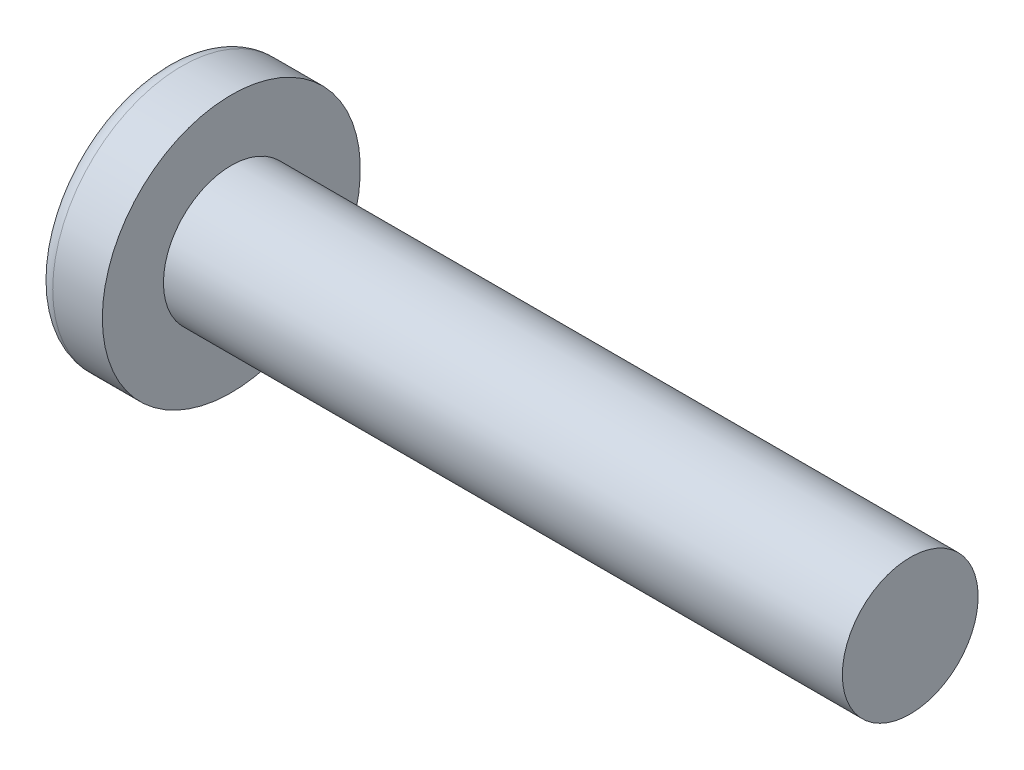
SolidWorks part; units mm, degrees
ref_plane "Plane1" through (0, 0, 0) normal (0, 0, 1) x (1, 0, 0)
ref_plane "Plane2" through (0, 0, 0) normal (0, 1, 0) x (1, 0, 0)
ref_plane "Plane3" through (0, 0, 0) normal (1, 0, 0) x (0, 0, -1)
other "Configuration Table"
sketch "BodySke" plane through (0, 0, 0) normal (0, 0, 1) x (1, 0, 0)
  line L0 (3.7, 2.5) -> (3.7, 4.75)
  line L1 (4.5, 6.35) -> (4.5, -3.175) construction
  line L2 (-25.4, 0) -> (127, 0) construction
  line L3 (28.7, 0) -> (0, 0)
  line L4 (3.7, 2.5) -> (28.7, 2.5)
  line L5 (28.7, 2.5) -> (28.7, 0)
  line L6 (1.8732, 4.75) -> (3.7, 4.75)
  line L7 (3.7, -2.5) -> (28.7, -2.5) construction
  line L8 (3.7, 6.35) -> (3.7, -3.175) construction
  arc A0 (1.3764, 4.4865) -> (0, 0) centre (8, 0) ccw
  arc A2 (1.3764, 4.4865) -> (1.8732, 4.75) centre (1.8732, 4.15) cw
  dimension "Head_fillet_rad" = 0.6
  dimension "Length" = 25
  dimension "Head_ht" = 3.7
  dimension "Head_dia" = 9.5
  dimension "Diameter" = 5
  dimension "Advance" = 0.7806
revolve "Base-Revolve" add sketch "BodySke" angle 360 about L2
cosmetic thread "ThreadCosmetic" [suppressed] parameters "Thread_length"=24.2, "Thread_minor"=4.11
sketch "Sketch3" plane through (0, 0, 0) normal (1, 0, 0) x (0, 0, -1)
  line L0 (0.5, -2.45) -> (-0.5, -2.45)
  line L1 (0.5, -2.45) -> (0.5, 2.45)
  line L2 (-0.5, 2.45) -> (0.5, 2.45)
  line L3 (-0.5, 2.45) -> (-0.5, -2.45)
  dimension "D1" = 2.45
  dimension "D2" = 0.5
ref_plane "Plane4" through (2.95, 0, 0) normal (1, 0, 0) x (0, 0, -1)
sketch "Sketch4" plane through (2.95, 0, 0) normal (1, 0, 0) x (0, 0, -1)
  line L0 (0.25, -0.25) -> (-0.25, -0.25)
  line L1 (0.25, -0.25) -> (0.25, 0.25)
  line L2 (-0.25, 0.25) -> (0.25, 0.25)
  line L3 (-0.25, 0.25) -> (-0.25, -0.25)
  dimension "D2" = 0.5
  dimension "D1" = 0.5
  dimension "D3" = 0.25
  dimension "D4" = 0.25
loft "Cut-Loft1" cut profiles "Sketch3", "Sketch4"
pattern_circular "CirPattern1" count 2 every 90 about axis through (-25.4, 0, 0) along (1, 0, 0) of "Cut-Loft1"
sketch "ThdSchSke" plane through (0, 0, 0) normal (0, 0, 1) x (1, 0, 0)
  line L0 (4.5, -2.055) -> (4.1884, -2.5)
  line L1 (4.5, -2.055) -> (4.8116, -2.5)
  line L2 (4.8116, -2.5) -> (4.8116, -3.125)
  line L3 (-3.175, 0) -> (5.1513, 0) construction
  line L5 (4.8116, -3.125) -> (4.1884, -3.125)
  line L6 (4.1884, -3.125) -> (4.1884, -2.5)
  dimension "Thread_minor" = 4.11
  dimension "Diameter" = 5
  dimension "Start" = 4.5
revolve "ThreadSchematic" [suppressed] cut sketch "ThdSchSke" angle 360 about L3
pattern_linear "ThdSchPat" [suppressed]
equation "\"D1@Sketch3\" = \"Cross_dia@Sketch3\" / 2"
equation "\"D2@Sketch3\" = \"Cross_width@Sketch3\" / 2"
equation "\"D1@Sketch4\" = \"Cross_width@Sketch3\" *.5"
equation "\"D2@Sketch4\" = \"D1@Sketch4\""
equation "\"D3@Sketch4\" = \"D1@Sketch4\" / 2"
equation "\"D4@Sketch4\" = \"D2@Sketch4\" / 2"
equation "\"Thread_length@ThreadCosmetic\" = ((sgn( (\"Length@BodySke\" - \"Advance@BodySke\" ) - \"Thread_nom@BodySke\" )-1)*( (\"Length@BodySke\" - \"Advance@BodySke\" ) - \"Thread_nom@BodySke\" ))/-2+ \"Thread_nom@BodySke\""
equation "\"Thread_minor@ThdSchSke\" = \"Thread_minor@ThreadCosmetic\""
equation "\"Diameter@ThdSchSke\" = \"Diameter@BodySke\""
equation "\"Overcut@ThdSchSke\" = \"Diameter@BodySke\" * 1.25"
equation "\"Start@ThdSchSke\" = \"Head_ht@BodySke\" + \"Length@BodySke\" - \"Thread_length@ThreadCosmetic\"  '---Non-countersunk---"
equation "\"Num_threads@ThdSchPat\" = int( \"Thread_length@ThreadCosmetic\" / \"Advance@BodySke\" + 0.999 )  + 1"
equation "\"Advance@ThdSchPat\" = \"Thread_length@ThreadCosmetic\" /  (\"Num_threads@ThdSchPat\" - 1) 'relax it"
